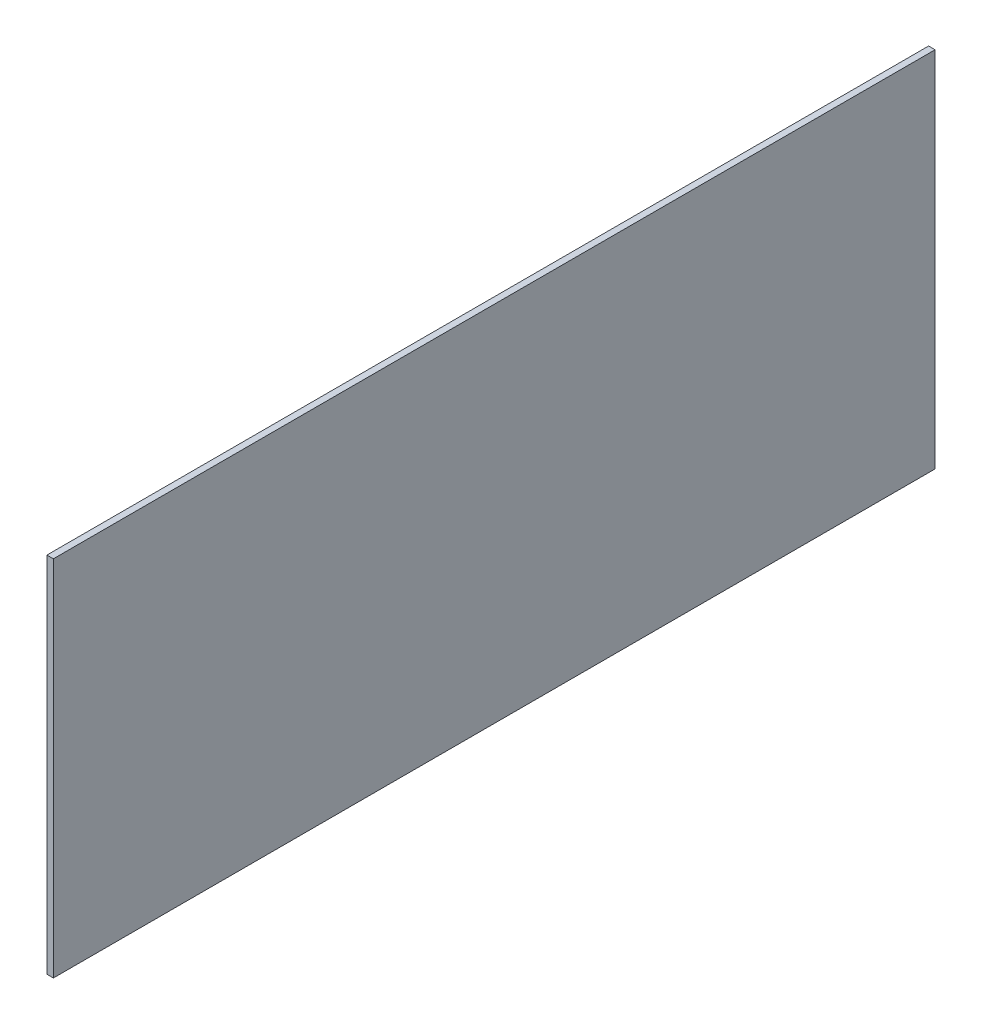
SolidWorks part; units mm, degrees
ref_plane "Ebene vorne" through (0, 0, 0) normal (0, 0, 1) x (1, 0, 0)
ref_plane "Ebene oben" through (0, 0, 0) normal (0, 1, 0) x (1, 0, 0)
ref_plane "Ebene rechts" through (0, 0, 0) normal (1, 0, 0) x (0, 0, -1)
sketch "Skizze1" plane through (0, 0, 0) normal (1, 0, 0) x (0, 0, -1)
  line L1 (-340, 140) -> (340, 140)
  line L2 (-340, 140) -> (-340, -140)
  line L3 (-340, -140) -> (340, -140)
  line L4 (340, 140) -> (340, -140)
  line L5 (-340, 140) -> (340, -140) construction
  line L6 (-340, -140) -> (340, 140) construction
  point P0 (0, 0)
  dimension "D1" = 680
  dimension "D2" = 280
extrude "Aufsatz-Linear austragen1" add sketch "Skizze1" along normal blind 5
